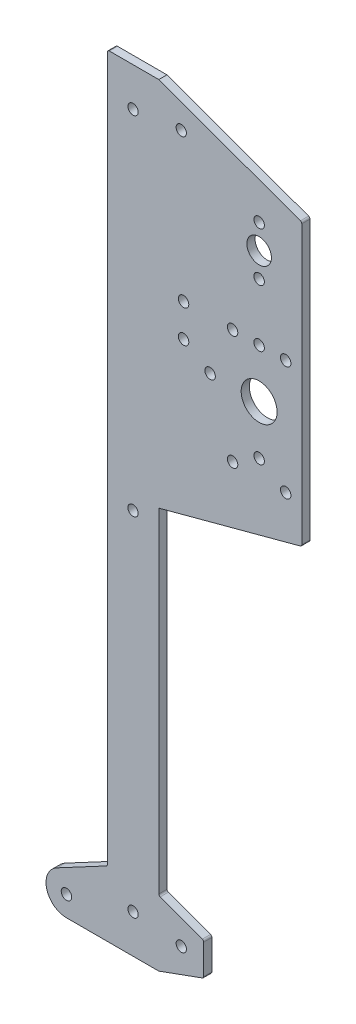
SolidWorks part; units mm, degrees
ref_plane "Front Plane" through (0, 0, 0) normal (0, 0, 1) x (1, 0, 0)
ref_plane "Top Plane" through (0, 0, 0) normal (0, 1, 0) x (1, 0, 0)
ref_plane "Right Plane" through (0, 0, 0) normal (1, 0, 0) x (0, 0, -1)
sketch "Sketch1" plane through (0, 0, 0) normal (0, 0, 1) x (1, 0, 0)
  line L1 (-10, 150) -> (10, 150)
  line L2 (-10, 150) -> (-10, -150)
  line L3 (-10, -150) -> (10, -150)
  line L4 (10, 150) -> (10, -150)
  line L5 (-10, 150) -> (10, -150) construction
  line L6 (-10, -150) -> (10, 150) construction
  point P0 (0, 0)
  dimension "D1" = 300
  dimension "20mm" = 20
extrude "Boss-Extrude1" add sketch "Sketch1" along normal blind 3.175
sketch "Sketch2" plane through (0, 0, 3.175) normal (0, 0, 1) x (1, 0, 0)
  line L0 (10, 150) -> (27.4625, 143.65)
  line L1 (27.4625, 143.65) -> (27.4625, 130.95)
  line L2 (27.4625, 130.95) -> (10, 124.6)
  line L3 (10, -150) -> (10, 150) construction
  line L4 (10, 124.6) -> (10, 150)
  line L5 (10, 150) -> (-10, 150) construction
  line L6 (-10, 0) -> (10, 0) construction
  line L7 (-10, 150) -> (-10, -150) construction
  line L8 (10, -124.6) -> (10, -150)
  line L9 (27.4625, -130.95) -> (10, -124.6)
  line L10 (27.4625, -143.65) -> (27.4625, -130.95)
  line L11 (10, -150) -> (27.4625, -143.65)
  line L12 (18.7312, 140.475) -> (18.7312, 134.125) construction
  circle A1 centre (18.7312, 134.125) radius 5 construction
  circle A2 centre (18.7312, 140.475) radius 2 construction
  circle A4 centre (18.7312, -134.125) radius 5 construction
  circle A5 centre (18.7312, -134.125) radius 2 construction
  circle A6 centre (18.7312, 137.3) radius 2
  circle A7 centre (18.7312, -137.3) radius 2
  point P3 (27.4625, 137.3)
  point P8 (10, 137.3)
  point P13 (18.7312, 127.775)
  point P31 (27.4625, -137.3)
  dimension "D3" = 4
  dimension "D4" = 10
  dimension "D1" = 17.4625
  dimension "2.5" = 25.4
  dimension "D2" = 12.7
  dimension "D5" = 9.525
  dimension "D6" = 9.525
extrude "Boss-Extrude2" add sketch "Sketch2" against normal up to surface (3.175 mm away) up to face at (0, 0, 0)
sketch "Sketch4" plane through (0, 0, 3.175) normal (0, 0, 1) x (1, 0, 0)
  line L0 (0, 150) -> (0, 135) construction
  line L2 (0, 135) -> (0, 0) construction
  line L3 (0, 0) -> (0, -135) construction
  line L4 (0, -135) -> (0, -150) construction
  line L6 (10, 150) -> (-10, 150) construction
  line L7 (-10, -150) -> (10, -150) construction
  circle A0 centre (0, -135) radius 2
  circle A1 centre (0, 0) radius 2
  circle A2 centre (0, 135) radius 2
  dimension "D4" = 4
  dimension "D1" = 15
  dimension "D2" = 135
  dimension "D3" = 135
extrude "Cut-Extrude1" cut sketch "Sketch4" against normal through all
sketch "Sketch5" plane through (0, 0, 3.175) normal (0, 0, 1) x (1, 0, 0)
  line L0 (-10, 111.9) -> (-41.75, 118.25)
  line L1 (-10, 150) -> (-10, -150) construction
  line L2 (-41.75, 118.25) -> (-41.75, 137.3)
  line L3 (-41.75, 137.3) -> (-10, 137.3)
  line L4 (-10, 137.3) -> (-10, 111.9)
  line L5 (10, 150) -> (-10, 150) construction
  line L6 (-41.75, 133.3313) -> (-37.7813, 133.3313) construction
  line L7 (-13.9688, 133.3313) -> (-10, 133.3313) construction
  line L8 (-10, -150) -> (-25.875, -150)
  line L9 (-29.6103, -135.0588) -> (-10, -124.6)
  line L10 (-10, -124.6) -> (-10, -150)
  circle A0 centre (-13.9688, 133.3313) radius 2.032
  circle A1 centre (-13.9688, 122.2188) radius 2.032
  circle A2 centre (-37.7813, 133.3313) radius 2.032
  circle A3 centre (-37.7813, 122.2188) radius 2.032
  arc A4 (-25.875, -150) -> (-29.6103, -135.0588) centre (-25.875, -142.0625) cw
  circle A5 centre (-25.875, -142.0625) radius 2.032
  point P24 (-25.875, 137.3)
  dimension "D5" = 4.064
  dimension "D9" = 4.064
  dimension "D10" = 7.9375
  dimension "D1" = 12.7
  dimension "D2" = 19.05
  dimension "D3" = 25.4
  dimension "D4" = 31.75
  dimension "D6" = 11.1125
  dimension "D7" = 23.8125
  dimension "D8" = 3.9688
  dimension "D11" = 25.4
extrude "Boss-Extrude3" [suppressed] add sketch "Sketch5" against normal up to surface (1.5875 mm away) up to face at (2, -135, 0)
fillet "Fillet3" [suppressed] radius 1.5875
sketch "Sketch6" plane through (0, 0, 3.175) normal (0, 0, 1) x (1, 0, 0)
  line L0 (-10, -124.6) -> (-10, -150) construction
  line L1 (-10, -150) -> (-25.875, -150) construction
  line L2 (-29.6103, -135.0588) -> (-10, -124.6) construction
  line L3 (-10, -124.6) -> (-10, -150)
  line L4 (-10, -150) -> (-25.875, -150)
  line L5 (-29.6103, -135.0588) -> (-10, -124.6)
  circle A0 centre (-25.875, -142.0625) radius 2.032 construction
  arc A1 (-29.6103, -135.0588) -> (-25.875, -150) centre (-25.875, -142.0625) ccw construction
  circle A2 centre (-25.875, -142.0625) radius 2.032
  arc A3 (-29.6103, -135.0588) -> (-25.875, -150) centre (-25.875, -142.0625) ccw
extrude "Boss-Extrude4" add sketch "Sketch6" against normal up to vertex (3.175 mm away) up to point (-10, -150, 0)
fillet "Fillet4" radius 0.7937 8 edges at (10, 124.6, 1.5875) (27.4625, 130.95, 1.5875) (-10, 150, 1.5875) (27.4625, 143.65, 1.5875) (-10, -124.6, 1.5875) (10, -124.6, 1.5875) (27.4625, -130.95, 1.5875) (27.4625, -143.65, 1.5875)
fillet "Fillet5" [suppressed] radius 1.5875
sketch "Sketch7" plane through (0, 0, 0) normal (0, 0, -1) x (-1, 0, 0)
  line L0 (-26.94, 143.84) -> (-65.04, 129.9855)
  line L1 (-65.5625, 129.2395) -> (-65.5625, 21.2895)
  line L2 (-64.9742, 20.5228) -> (-10, 5.7925)
  line L3 (-10, 150) -> (-26.94, 143.84) construction
  line L4 (-10, 5.7925) -> (-10, 124.044)
  line L5 (-27.4625, 143.094) -> (-27.4625, 131.506) construction
  line L6 (-26.94, 130.76) -> (-10.5225, 124.79) construction
  line L7 (-27.4625, 143.094) -> (-27.4625, 131.506)
  line L8 (-26.94, 130.76) -> (-10.5225, 124.79)
  line L10 (-10, 150) -> (9.2063, 150) construction
  line L11 (-48.989, 57.925) -> (-48.989, 61.1) construction
  line L12 (-38.6703, 35.7) -> (-59.3078, 35.7) construction
  line L13 (-38.6703, 35.7) -> (-38.6703, 80.15) construction
  line L14 (-38.6703, 80.15) -> (-59.3078, 80.15) construction
  line L15 (-59.3078, 35.7) -> (-59.3078, 80.15) construction
  line L16 (-38.6703, 35.7) -> (-59.3078, 80.15) construction
  line L17 (-38.6703, 80.15) -> (-59.3078, 35.7) construction
  line L18 (-48.989, 111.9) -> (-48.989, 61.1) construction
  line L19 (-10, -124.044) -> (-10, 124.044) construction
  arc A0 (-65.04, 129.9855) -> (-65.5625, 129.2395) centre (-64.7687, 129.2395) ccw
  arc A1 (-65.5625, 21.2895) -> (-64.9742, 20.5228) centre (-64.7687, 21.2895) ccw
  arc A2 (-26.94, 143.84) -> (-27.4625, 143.094) centre (-26.6688, 143.094) ccw construction
  arc A3 (-27.4625, 131.506) -> (-26.94, 130.76) centre (-26.6688, 131.506) ccw construction
  arc A4 (-10, 124.044) -> (-10.5225, 124.79) centre (-10.7937, 124.044) ccw construction
  arc A5 (-26.94, 143.84) -> (-27.4625, 143.094) centre (-26.6688, 143.094) ccw
  arc A6 (-27.4625, 131.506) -> (-26.94, 130.76) centre (-26.6688, 131.506) ccw
  arc A7 (-10, 124.044) -> (-10.5225, 124.79) centre (-10.7937, 124.044) ccw
  arc A8 (10, 149.2063) -> (9.2063, 150) centre (9.2063, 149.2063) ccw construction
  circle A9 centre (-48.989, 111.9) radius 4.7625
  circle A10 centre (-48.989, 61.1) radius 6.985
  circle A11 centre (-59.3078, 80.15) radius 2.032
  circle A12 centre (-59.3078, 35.7) radius 2.032
  circle A13 centre (-38.6703, 35.7) radius 2.032
  circle A14 centre (-38.6703, 80.15) radius 2.032
  point P32 (-48.989, 57.925)
  dimension "D4" = 9.525
  dimension "D6" = 13.97
  dimension "D11" = 4.064
  dimension "D1" = 38.1
  dimension "D2" = 107.95
  dimension "D3" = 16.5735
  dimension "D5" = 38.1
  dimension "D7" = 3.175
  dimension "D8" = 44.45
  dimension "D9" = 50.8
  dimension "D10" = 20.6375
  dimension "D12" = 75
extrude "Boss-Extrude5" add sketch "Sketch7" against normal up to surface (3.175 mm away) up to face at (2, -135, 3.175)
sketch "Sketch8" plane through (0, 0, 3.175) normal (0, 0, 1) x (1, 0, 0)
  line L0 (48.989, 61.1) -> (48.989, 80.15) construction
  line L1 (48.989, 61.1) -> (29.939, 61.1) construction
  line L2 (48.989, 61.1) -> (48.989, 42.05) construction
  line L3 (48.989, 111.9) -> (48.989, 121.425) construction
  line L4 (48.989, 111.9) -> (48.989, 102.375) construction
  line L5 (19.6203, 80.15) -> (19.6203, 67.45) construction
  circle A0 centre (48.989, 80.15) radius 2.032
  circle A1 centre (29.939, 61.1) radius 2.032
  circle A2 centre (48.989, 42.05) radius 2.032
  circle A3 centre (59.3078, 80.15) radius 2.032 construction
  circle A4 centre (48.989, 121.425) radius 2.032
  circle A5 centre (48.989, 102.375) radius 2.032
  circle A6 centre (19.6203, 67.45) radius 2.032
  circle A7 centre (19.6203, 80.15) radius 2.032
  dimension "D2" = 9.525
  dimension "D1" = 19.05
  dimension "D3" = 12.7
  dimension "D4" = 6.35
  dimension "D5" = 10.3187
extrude "Cut-Extrude2" cut sketch "Sketch8" against normal through all
